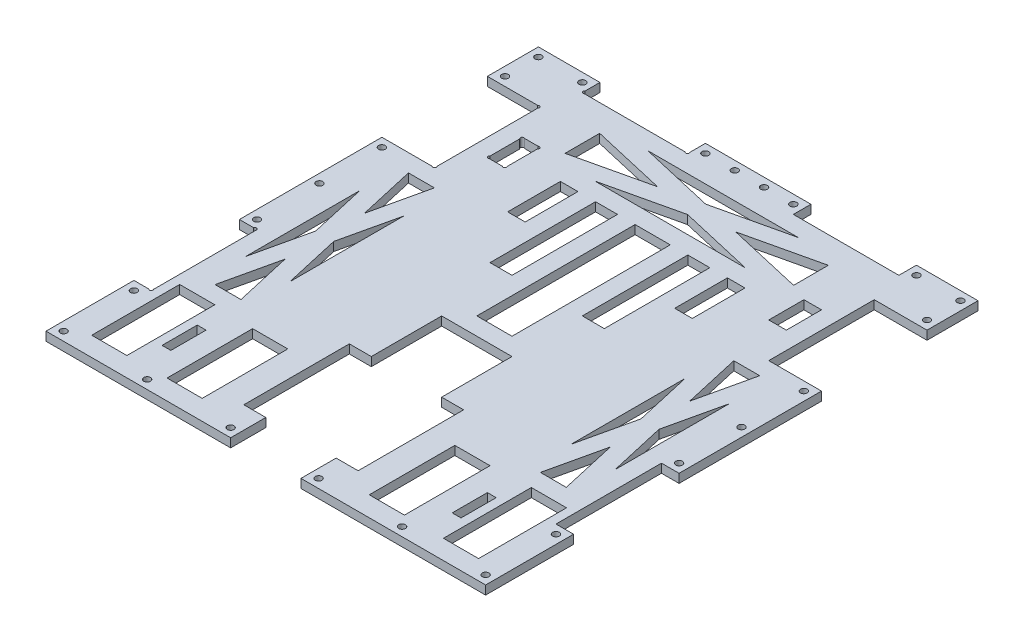
SolidWorks part; units mm, degrees
material "7050-T73510"
ref_plane "Front Plane" through (0, 0, 0) normal (0, 0, 1) x (1, 0, 0)
ref_plane "Top Plane" through (0, 0, 0) normal (0, 1, 0) x (1, 0, 0)
ref_plane "Right Plane" through (0, 0, 0) normal (1, 0, 0) x (0, 0, -1)
sketch "Sketch1" plane through (0, 0, 0) normal (0, 1, 0) x (1, 0, 0)
  line L1 (-158.75, -177.8) -> (158.75, -177.8)
  line L2 (-158.75, -177.8) -> (-158.75, 177.8)
  line L3 (-158.75, 177.8) -> (158.75, 177.8)
  line L4 (158.75, -177.8) -> (158.75, 177.8)
  line L5 (-158.75, -177.8) -> (158.75, 177.8) construction
  line L6 (-158.75, 177.8) -> (158.75, -177.8) construction
  point P0 (0, 0)
  dimension "D1" = 355.6
  dimension "D2" = 317.5
extrude "Boss-Extrude1" add sketch "Sketch1" along normal blind 6.35
sketch "Sketch2" plane through (0, 6.35, 0) normal (0, 1, 0) x (1, 0, 0)
  line L0 (-158.75, -177.8) -> (158.75, -177.8) construction
  line L1 (-25.4, -25.4) -> (25.4, -25.4)
  line L2 (-25.4, -25.4) -> (-25.4, -177.8)
  line L3 (-25.4, -177.8) -> (25.4, -177.8)
  line L4 (25.4, -25.4) -> (25.4, -177.8)
  line L5 (-25.4, -25.4) -> (25.4, -177.8) construction
  line L6 (-25.4, -177.8) -> (25.4, -25.4) construction
  point P0 (0, -101.6)
  dimension "D1" = 152.4
  dimension "D2" = 50.8
extrude "Cut-Extrude1" cut sketch "Sketch2" against normal through all
sketch "Sketch3" plane through (0, 6.35, 0) normal (0, 1, 0) x (1, 0, 0)
  line L0 (158.75, -177.8) -> (158.75, 177.8) construction
  line L5 (146.05, 140.97) -> (120.65, 140.97)
  line L11 (146.05, 140.97) -> (146.05, 64.77)
  line L13 (146.05, 64.77) -> (120.65, 64.77)
  line L15 (120.65, 140.97) -> (120.65, 64.77)
  line L16 (158.75, 177.8) -> (-158.75, 177.8) construction
  line L17 (107.95, 90.17) -> (95.25, 90.17)
  line L18 (107.95, 90.17) -> (107.95, 115.57)
  line L19 (107.95, 115.57) -> (95.25, 115.57)
  line L20 (95.25, 90.17) -> (95.25, 115.57)
  line L21 (0, -3.4925) -> (0, 3.4925) construction
  line L22 (-95.25, 90.17) -> (-95.25, 115.57)
  line L23 (-107.95, 115.57) -> (-95.25, 115.57)
  line L24 (-107.95, 90.17) -> (-107.95, 115.57)
  line L25 (-107.95, 90.17) -> (-95.25, 90.17)
  line L26 (-120.65, 140.97) -> (-120.65, 64.77)
  line L27 (-146.05, 64.77) -> (-120.65, 64.77)
  line L28 (-146.05, 140.97) -> (-146.05, 64.77)
  line L29 (-146.05, 140.97) -> (-120.65, 140.97)
  point P14 (107.95, 102.87)
  point P15 (120.65, 102.87)
  dimension "D1" = 25.4
  dimension "D2" = 12.7
  dimension "D3" = 12.7
  dimension "D4" = 12.7
  dimension "D5" = 25.4
  dimension "D6" = 76.2
  dimension "D7" = 36.83
extrude "Cut-Extrude2" cut sketch "Sketch3" against normal through all contours L5 L15 L13 L11 | L20 L17 L18 L19 | L29 L28 L27 L26 | L24 L25 L22 L23 | L26 L27 L28 L29 region at (133.35, 6.35, -102.87) region at (101.6, 6.35, -102.87) region at (-101.6, 6.35, -102.87) region at (-133.35, 6.35, -102.87)
sketch "Sketch4" plane through (0, 6.35, 0) normal (0, 1, 0) x (1, 0, 0)
  line L0 (-158.75, 177.8) -> (-158.75, -177.8) construction
  line L1 (-158.75, 140.97) -> (-146.05, 140.97)
  line L2 (-158.75, 140.97) -> (-158.75, 64.77)
  line L3 (-158.75, 64.77) -> (-146.05, 64.77)
  line L4 (-146.05, 140.97) -> (-146.05, 64.77)
  line L5 (0, -3.4925) -> (0, 3.4925) construction
  line L6 (-158.75, -114.3) -> (-146.05, -114.3)
  line L7 (-158.75, -114.3) -> (-158.75, -38.1)
  line L8 (-158.75, -38.1) -> (-146.05, -38.1)
  line L9 (-146.05, -114.3) -> (-146.05, -38.1)
  line L10 (158.75, 64.77) -> (146.05, 64.77)
  line L11 (146.05, 140.97) -> (146.05, 64.77)
  line L12 (158.75, 140.97) -> (146.05, 140.97)
  line L13 (158.75, 140.97) -> (158.75, 64.77)
  line L14 (158.75, -38.1) -> (146.05, -38.1)
  line L15 (146.05, -114.3) -> (146.05, -38.1)
  line L16 (158.75, -114.3) -> (146.05, -114.3)
  line L17 (158.75, -114.3) -> (158.75, -38.1)
  line L18 (158.75, 177.8) -> (-158.75, 177.8) construction
  line L19 (114.3, 165.1) -> (38.1, 165.1)
  line L20 (-114.3, 177.8) -> (-38.1, 177.8)
  line L21 (-114.3, 177.8) -> (-114.3, 165.1)
  line L22 (-114.3, 165.1) -> (-38.1, 165.1)
  line L23 (-38.1, 177.8) -> (-38.1, 165.1)
  line L24 (38.1, 177.8) -> (38.1, 165.1)
  line L25 (114.3, 177.8) -> (38.1, 177.8)
  line L26 (114.3, 177.8) -> (114.3, 165.1)
  line L27 (-25.4, -25.4) -> (-25.4, -177.8) construction
  line L28 (-25.4, -152.4) -> (-41.275, -152.4)
  line L29 (-25.4, -152.4) -> (-25.4, -76.2)
  line L30 (-25.4, -76.2) -> (-41.275, -76.2)
  line L31 (-41.275, -152.4) -> (-41.275, -76.2)
  line L32 (-158.75, -177.8) -> (-25.4, -177.8) construction
  line L33 (25.4, 101.6) -> (41.275, 101.6)
  line L34 (-25.4, 25.4) -> (-41.275, 25.4)
  line L35 (-25.4, 25.4) -> (-25.4, 101.6)
  line L36 (-25.4, 101.6) -> (-41.275, 101.6)
  line L37 (-41.275, 25.4) -> (-41.275, 101.6)
  line L38 (41.275, 25.4) -> (41.275, 101.6)
  line L39 (25.4, 25.4) -> (41.275, 25.4)
  line L40 (25.4, 25.4) -> (25.4, 101.6)
  line L41 (25.4, -76.2) -> (41.275, -76.2)
  line L42 (41.275, -152.4) -> (41.275, -76.2)
  line L43 (25.4, -152.4) -> (41.275, -152.4)
  line L44 (25.4, -152.4) -> (25.4, -76.2)
  dimension "D1" = 12.7
  dimension "D2" = 12.7
  dimension "D3" = 76.2
  dimension "D4" = 76.2
  dimension "D5" = 36.83
  dimension "D6" = 215.9
  dimension "D7" = 12.7
  dimension "D8" = 76.2
  dimension "D9" = 76.2
  dimension "D10" = 15.875
  dimension "D11" = 76.2
  dimension "D12" = 25.4
  dimension "D13" = 76.2
  dimension "D14" = 15.875
  dimension "D15" = 203.2
  dimension "D16" = 50.8
extrude "Cut-Extrude3" cut sketch "Sketch4" against normal through all
sketch "Sketch5" plane through (0, 6.35, 0) normal (0, 1, 0) x (1, 0, 0)
  line L0 (-41.275, -76.2) -> (-41.275, -152.4) construction
  line L5 (-41.275, 101.6) -> (-41.275, 25.4) construction
  line L6 (-85.725, -101.6) -> (-60.325, -101.6)
  line L7 (-133.35, -87.63) -> (-101.6, -87.63)
  line L8 (-133.35, -87.63) -> (-133.35, 52.07)
  line L9 (-133.35, 52.07) -> (-101.6, 52.07)
  line L10 (-101.6, -87.63) -> (-101.6, 52.07)
  line L11 (-133.35, -87.63) -> (-101.6, 52.07) construction
  line L12 (-133.35, 52.07) -> (-101.6, -87.63) construction
  line L13 (-82.55, 114.3) -> (82.55, 114.3)
  line L14 (-82.55, 114.3) -> (-82.55, 152.4)
  line L15 (-82.55, 152.4) -> (82.55, 152.4)
  line L16 (82.55, 114.3) -> (82.55, 152.4)
  line L17 (-82.55, 114.3) -> (82.55, 152.4) construction
  line L18 (-82.55, 152.4) -> (82.55, 114.3) construction
  line L23 (0, -3.4925) -> (0, 3.4925) construction
  line L24 (-12.7, -12.7) -> (12.7, -12.7)
  line L25 (-146.05, -114.3) -> (-146.05, -38.1) construction
  line L26 (-53.975, 101.6) -> (-66.675, 101.6)
  line L27 (-53.975, 101.6) -> (-53.975, 63.5)
  line L28 (-158.75, 64.77) -> (-158.75, -38.1) construction
  line L29 (-158.75, 64.77) -> (-120.65, 64.77) construction
  line L30 (-85.725, -101.6) -> (-85.725, -163.4194)
  line L31 (-12.7, -12.7) -> (-12.7, 101.6)
  line L32 (-12.7, 101.6) -> (12.7, 101.6)
  line L33 (12.7, -12.7) -> (12.7, 101.6)
  line L34 (-53.975, 63.5) -> (-66.675, 63.5)
  line L35 (-66.675, 101.6) -> (-66.675, 63.5)
  line L36 (53.975, 63.5) -> (66.675, 63.5)
  line L37 (-25.4, 25.4) -> (-25.4, 101.6) construction
  line L38 (-25.4, 101.6) -> (-41.275, 101.6) construction
  line L39 (-95.25, 90.17) -> (-95.25, 115.57) construction
  line L40 (-114.3, 165.1) -> (-38.1, 165.1) construction
  line L41 (-85.725, -163.4194) -> (-60.325, -163.4194)
  line L42 (-60.325, -101.6) -> (-60.325, -163.4194)
  line L43 (-139.5421, 50.6627) -> (-107.7921, -89.0373)
  line L44 (-127.1579, -89.0373) -> (-95.4079, 50.6627)
  line L45 (66.675, 101.6) -> (66.675, 63.5)
  line L46 (53.975, 101.6) -> (66.675, 101.6)
  line L47 (-83.9779, 146.2126) -> (81.1221, 108.1126)
  line L48 (-81.1221, 108.1126) -> (83.9779, 146.2126)
  line L49 (53.975, 101.6) -> (53.975, 63.5)
  line L51 (-127.1579, 53.4773) -> (-95.4079, -86.2227)
  line L52 (-139.5421, -86.2227) -> (-107.7921, 53.4773)
  line L55 (-81.1221, 158.5874) -> (83.9779, 120.4874)
  line L56 (-83.9779, 120.4874) -> (81.1221, 158.5874)
  line L57 (-139.7, -100.33) -> (-114.3, -100.33)
  line L58 (-139.7, -100.33) -> (-139.7, -163.83)
  line L59 (-139.7, -163.83) -> (-114.3, -163.83)
  line L60 (-114.3, -100.33) -> (-114.3, -163.83)
  line L63 (-107.95, -144.78) -> (-101.6, -144.78)
  line L64 (-107.95, -144.78) -> (-107.95, -119.38)
  line L65 (-107.95, -119.38) -> (-101.6, -119.38)
  line L66 (-101.6, -144.78) -> (-101.6, -119.38)
  line L67 (-107.95, -144.78) -> (-101.6, -119.38) construction
  line L68 (-107.95, -119.38) -> (-101.6, -144.78) construction
  point P5 (-117.475, -17.78)
  point P10 (0, 133.35)
  point P15 (0, 44.45)
  point P34 (-104.775, -132.08)
  point P45 (-33.3375, 101.6)
  point P87 (-114.3, -132.08)
  dimension "D3" = 12.7
  dimension "D4" = 19.05
  dimension "D5" = 139.7
  dimension "D6" = 25.4
  dimension "D7" = 12.7
  dimension "D8" = 31.75
  dimension "D9" = 25.4
  dimension "D10" = 12.7
  dimension "D11" = 165.1
  dimension "D12" = 12.7
  dimension "D13" = 12.7
  dimension "D14" = 12.7
  dimension "D17" = 25.4
  dimension "D18" = 63.5
  dimension "D19" = 12.7
  dimension "D20" = 6.35
  dimension "D21" = 38.1
  dimension "D22" = 38.1
  dimension "D23" = 25.4
  dimension "D15" = 114.3
  dimension "D16" = 12.7
extrude "Cut-Extrude4" cut sketch "Sketch5" against normal through all contours L44 L7 L43 | L8 L52 L43 | L51 L52 L9 | L44 L51 L10 | L33 | L32 | L31 | L24 | L48 L13 L47 | L48 L55 L16 | L55 L56 L15 | L14 L56 L47 | L60 L57 L58 L59 | L63 L66 L65 L64 | L42 L6 L30 L41 | L26 L35 L34 L27 | L46 L49 L36 L45 region at (-73.025, 6.35, 132.5097) region at (-117.475, 6.35, 73.8975) region at (-130.229, 6.35, 17.78) region at (-104.721, 6.35, 17.78) region at (-117.475, 6.35, -38.3375) region at (0, 6.35, -118.4777) region at (-64.4466, 6.35, -133.35) region at (64.4466, 6.35, -133.35) region at (0, 6.35, -148.2223) region at (0, 6.35, -44.45) region at (-60.325, 6.35, -82.55) region at (60.325, 6.35, -82.55) region at (-127, 6.35, 132.08) region at (-104.775, 6.35, 132.08)
mirror "Mirror1" about plane through (0, 0, 0) normal (1, 0, 0) of "Cut-Extrude4"
sketch "Sketch7" plane through (0, 6.35, 0) normal (0, 1, 0) x (1, 0, 0)
  line L0 (-158.75, -177.8) -> (-25.4, -177.8) construction
  line L1 (-158.75, -114.3) -> (-158.75, -177.8) construction
  line L2 (0, -3.4925) -> (0, 3.4925) construction
  line L3 (-158.75, 177.8) -> (-158.75, 140.97) construction
  line L4 (-114.3, 177.8) -> (-158.75, 177.8) construction
  line L6 (38.1, 177.8) -> (-38.1, 177.8) construction
  line L7 (-38.1, 165.1) -> (-38.1, 177.8) construction
  line L8 (-25.4, -152.4) -> (-25.4, -177.8) construction
  line L9 (-158.75, -114.3) -> (-146.05, -114.3) construction
  line L10 (-158.75, 64.77) -> (-158.75, -38.1) construction
  line L11 (-146.05, -38.1) -> (-158.75, -38.1) construction
  line L12 (-158.75, 64.77) -> (-120.65, 64.77) construction
  circle A0 centre (-152.4, -171.45) radius 2.413
  circle A14 centre (-152.4, 171.45) radius 2.413
  circle A15 centre (-120.65, 171.45) radius 2.413
  circle A16 centre (-152.4, 147.32) radius 2.413
  circle A34 centre (-31.75, 171.45) radius 2.413
  circle A35 centre (-10.5833, 171.45) radius 2.413
  circle A36 centre (10.5833, 171.45) radius 2.413
  circle A37 centre (31.75, 171.45) radius 2.413
  circle A38 centre (-31.75, -171.45) radius 2.413
  circle A39 centre (-92.075, -171.45) radius 2.413
  circle A40 centre (-152.4, -120.65) radius 2.413
  circle A41 centre (-152.4, -31.75) radius 2.413
  circle A42 centre (-152.4, 58.42) radius 2.413
  circle A43 centre (-152.4, 13.335) radius 2.413
  circle A44 centre (31.75, -171.45) radius 2.413
  circle A45 centre (152.4, 13.335) radius 2.413
  circle A46 centre (152.4, 58.42) radius 2.413
  circle A47 centre (152.4, -31.75) radius 2.413
  circle A48 centre (152.4, -120.65) radius 2.413
  circle A49 centre (92.075, -171.45) radius 2.413
  circle A50 centre (152.4, 147.32) radius 2.413
  circle A51 centre (120.65, 171.45) radius 2.413
  circle A52 centre (152.4, 171.45) radius 2.413
  circle A53 centre (152.4, -171.45) radius 2.413
  dimension "D1" = 4.826
  dimension "D6" = 6.35
  dimension "D9" = 4.826
  dimension "D14" = 4.826
  dimension "D4" = 4.826
  dimension "D5" = 4.826
  dimension "D8" = 4.826
  dimension "D20" = 4.826
  dimension "D24" = 4.826
  dimension "D25" = 4.826
  dimension "D2" = 6.35
  dimension "D3" = 6.35
  dimension "D7" = 60.325
  dimension "D10" = 6.35
  dimension "D11" = 6.35
  dimension "D15" = 6.35
  dimension "D16" = 6.35
  dimension "D18" = 6.35
  dimension "D19" = 6.35
  dimension "D21" = 6.35
  dimension "D22" = 6.35
  dimension "D23" = 6.35
  dimension "D26" = 45.085
  dimension "D12" = 2
  dimension "D13" = 2
  dimension "D17" = 4
extrude "Cut-Extrude6" cut sketch "Sketch7" against normal through all
sketch "Sketch8" plane through (0, 6.35, 0) normal (0, 1, 0) x (1, 0, 0)
  circle A0 centre (-39.0994, 165.8837) radius 1.27
  circle A1 centre (-113.5398, 166.1174) radius 1.27
  circle A2 centre (-121.56, 140.0841) radius 1.27
  circle A3 centre (-121.5656, 65.6501) radius 1.27
  circle A4 centre (-147.253, -38.507) radius 1.27
  circle A5 centre (-147.0444, -113.51) radius 1.27
  circle A6 centre (-107.1943, 114.5493) radius 1.27
  circle A7 centre (-96.0341, 114.5709) radius 1.27
  circle A8 centre (-107.1845, 91.1833) radius 1.27
  circle A10 centre (-96.2084, 91.0033) radius 1.27
extrude "Cut-Extrude7" cut sketch "Sketch8" against normal through all
